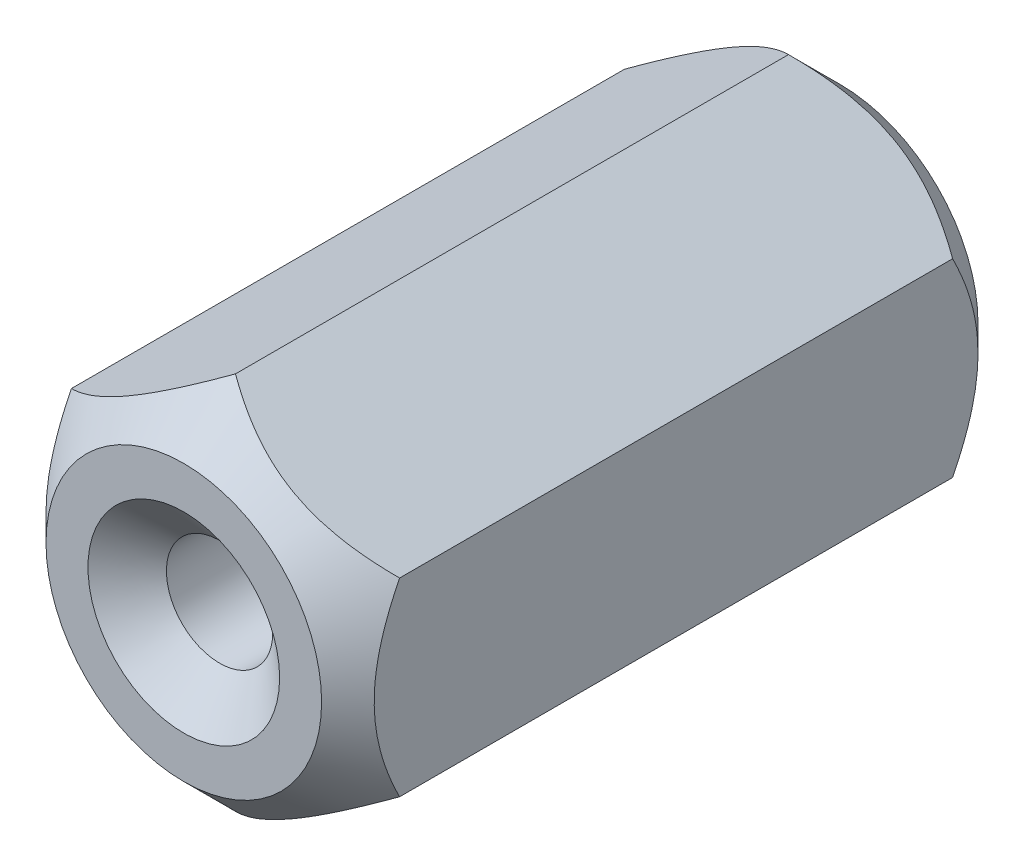
SolidWorks part; units mm, degrees
ref_plane "Front Plane" through (0, 0, 0) normal (0, 0, 1) x (1, 0, 0)
ref_plane "Top Plane" through (0, 0, 0) normal (0, 1, 0) x (1, 0, 0)
ref_plane "Right Plane" through (0, 0, 0) normal (1, 0, 0) x (0, 0, -1)
sketch "Sketch1" plane through (0, 0, 0) normal (0, 0, 1) x (1, 0, 0)
  line L1 (3.175, -1.8331) -> (3.175, 1.8331)
  line L2 (3.175, 1.8331) -> (0, 3.6662)
  line L3 (0, 3.6662) -> (-3.175, 1.8331)
  line L4 (-3.175, 1.8331) -> (-3.175, -1.8331)
  line L5 (-3.175, -1.8331) -> (0, -3.6662)
  line L6 (0, -3.6662) -> (3.175, -1.8331)
  circle A0 centre (0, 0) radius 3.175 construction
  dimension "D1" = 6.35
extrude "Boss-Extrude1" add sketch "Sketch1" along normal blind 6.35 and the other way blind 6.35
ref_axis "Axis1" through (0, 0, -0.635) along (0, 0, 1)
sketch "Sketch3" plane through (0, 0, 0) normal (1, 0, 0) x (0, 0, -1)
  line L0 (-6.35, 3.6662) -> (6.35, 3.6662) construction
  line L1 (-5.35, 3.6662) -> (-6.35, 2.6662)
  line L2 (-6.35, 1.8331) -> (-6.35, 3.6662) construction
  line L3 (-6.35, 2.6662) -> (-6.35, 3.6662)
  line L4 (-6.35, 3.6662) -> (-5.35, 3.6662)
  dimension "D1" = 1
  dimension "D2" = 45
revolve "Cut-Revolve2" cut sketch "Sketch3" angle 360 about axis through (0, 0, -0.635) along (0, 0, 1)
mirror "Mirror1" about plane through (0, 0, 0) normal (0, 0, 1) of "Cut-Revolve2"
hole_wizard "CSK for #1 Flat Head Machine Screw (100)1" positions "Sketch5" profile "Sketch4" countersink size "#1" standard "ANSI Inch" end condition through all
sketch "Sketch5" plane through (0, 0, 6.35) normal (0, 0, 1) x (1, 0, 0)
  point P0 (0, 0)
sketch "Sketch4" plane through (0, 0, 6.35) normal (1, 0, 0) x (0, -1, 0)
  line L0 (0, 0) -> (0, 12.7)
  line L1 (0, 12.7) -> (1.6637, 12.7)
  line L2 (1.0287, 12.065) -> (1.0287, 0.6927)
  line L3 (1.0287, 0.6927) -> (1.8542, 0)
  line L5 (1.8542, 0) -> (0, 0)
  line L6 (-1.0287, 0.6927) -> (-1.8542, 0) construction
  line L7 (1.6637, 12.7) -> (1.0287, 12.065)
  line L8 (-1.6637, 12.7) -> (-1.0287, 12.065) construction
  line L11 (0, -6.35) -> (0, 107.95) construction
  dimension "Thru Hole Dia." = 2.0574
  dimension "Thru Hole Depth" = 12.7
  dimension "Near C'Sink Dia." = 3.7084
  dimension "Near C'Sink Angle" = 100
  dimension "Far C'Sink Dia." = 3.3274
  dimension "Far C'Sink Angle" = 90
